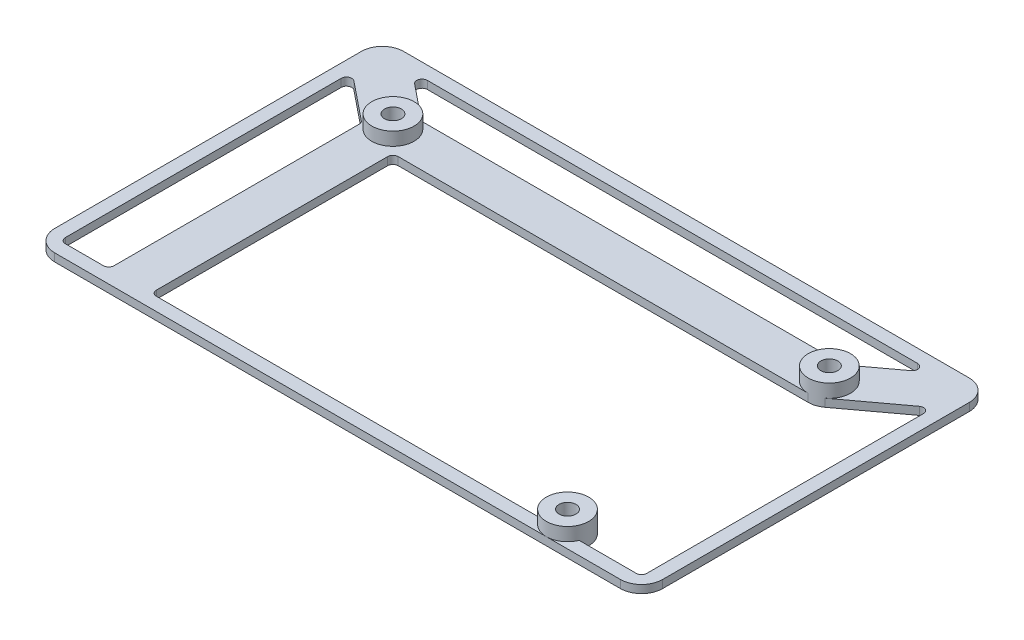
SolidWorks part; units mm, degrees
ref_plane "Alzado" through (0, 0, 0) normal (0, 0, 1) x (1, 0, 0)
ref_plane "Planta" through (0, 0, 0) normal (0, 1, 0) x (1, 0, 0)
ref_plane "Vista lateral" through (0, 0, 0) normal (1, 0, 0) x (0, 0, -1)
sketch "Croquis1" plane through (0, 0, 0) normal (0, 1, 0) x (1, 0, 0)
  line L1 (0, 4) -> (82.55, 4)
  line L2 (86.5486, -0.1052) -> (85.2786, -48.3652)
  line L3 (-2.0422, -3.4394) -> (79.2378, -51.6994)
  line L4 (0, -4) -> (82.55, -4)
  line L6 (1.098, 4) -> (83.3222, -44.8206)
  line L7 (78.5514, 0.1052) -> (77.2814, -48.1548)
  circle A1 centre (0, 0) radius 1.6
  circle A2 centre (82.55, 0) radius 1.6
  circle A3 centre (81.28, -48.26) radius 1.6
  circle A4 centre (0, 0) radius 4
  circle A5 centre (82.55, 0) radius 4
  circle A6 centre (81.28, -48.26) radius 4
  dimension "D1" = 3.2
  dimension "D7" = 8
  dimension "D3" = 82.55
  dimension "D6" = 1.27
extrude "Saliente-Extruir1" add sketch "Croquis1" along normal blind 1.5 contours A6 A3 | A6 L2 A5 L4 L7 L6 | A5 L1 L6 L4 L7 | A6 L7 L6 L4 A4 L3 | A6 L6 L7 | A5 L7 L4 | A5 A2 | A4 L4 L6 | A4 A1 region at (1.0289, 0, -3.7482) region at (43.2914, 0, -0.1461) region at (41.9356, 0, 25.0748) region at (7.0318, 0, 1.9303) region at (85.2984, 0, -2.7484) region at (77.8771, 0, 50.1382) region at (79.3885, 0, 3.0794) region at (78.8496, 0, 43.8567) region at (82.0449, 0, 23.7173)
extrude "Saliente-Extruir2" add sketch "Croquis1<3>" along normal blind 4 contours A4 A1 | A5 A2 | A6 A3 region at (1.0289, 0, -3.7482) region at (85.2984, 0, -2.7484) region at (77.8771, 0, 50.1382)
sketch "Croquis1<3>" plane through (0, 0, 0) normal (0, 1, 0) x (1, 0, 0) same geometry as "Croquis1"
sketch "Croquis2" plane through (0, 0, 0) normal (0, -1, 0) x (1, 0, 0)
  line L0 (14.5717, 4) -> (77.4607, 41.3403) construction
  line L1 (99.28, -13.74) -> (-15.72, -13.74)
  line L2 (99.28, -13.74) -> (99.28, 52.26)
  line L3 (99.28, 52.26) -> (-15.72, 52.26)
  line L4 (-15.72, -13.74) -> (-15.72, 52.26)
  line L5 (99.28, -13.74) -> (-15.72, 52.26) construction
  line L6 (99.28, 52.26) -> (-15.72, -13.74) construction
  line L7 (14.5717, 4) -> (78.4434, 4) construction
  line L8 (78.4434, 4) -> (77.4607, 41.3403) construction
  line L9 (14.5717, 4) -> (77.4607, 41.3403)
  line L10 (14.5717, 4) -> (78.4434, 4)
  line L11 (78.4434, 4) -> (77.4607, 41.3403)
  arc A1 (85.2786, 48.3652) -> (79.2378, 51.6994) centre (81.28, 48.26) ccw construction
  circle A2 centre (81.28, 48.26) radius 1.6 construction
  point P0 (41.78, 19.26)
  arc M5 (85.2786, 48.3652) -> (79.2378, 51.6994) centre (81.28, 48.26) ccw
  line M6 (79.2378, 51.6994) -> (-2.0422, 3.4394)
  arc M7 (-2.0422, 3.4394) -> (2.0422, -3.4394) centre (0, 0) ccw
  line M8 (2.0422, -3.4394) -> (1.098, -4)
  line M9 (1.098, -4) -> (82.55, -4)
  arc M10 (82.55, -4) -> (86.5486, 0.1052) centre (82.55, 0) ccw
  line M11 (86.5486, 0.1052) -> (85.2786, 48.3652)
  circle M12 centre (81.28, 48.26) radius 1.6
  circle M13 centre (82.55, 0) radius 1.6
  circle M14 centre (0, 0) radius 1.6
  line M15 (77.4607, 41.3403) -> (78.4434, 4)
  line M16 (78.4434, 4) -> (14.5717, 4)
  line M17 (14.5717, 4) -> (77.4607, 41.3403)
  dimension "D1" = 66
  dimension "D2" = 18
  dimension "D3" = 115
extrude "Saliente-Extruir7" add sketch "Croquis2" against normal up to surface (1.5 mm away) contours M11 M5 M6 M7 M8 M9 M10 M12 M14 M17 M15 M16 M13 | L4 L1 L2 L3 M5 M11 M10 M9 M8 M7 M6 region at (83.3272, 0, 50.3617) region at (41.78, 0, -12.4141) up to face at (56.8253, 1.5, 16.4468)
sketch "Croquis4" plane through (0, 1.5, 0) normal (0, 1, 0) x (1, 0, 0)
  line L4 (4, -4) -> (82.55, -4)
  line L5 (-4, 0) -> (-4, -49.76)
  line L6 (96.78, -49.76) -> (81.28, -49.76) construction
  line L8 (99.28, -52.26) -> (81.28, -52.26)
  line L9 (81.28, -52.26) -> (-15.72, -52.26)
  line L10 (-15.72, 13.74) -> (-15.72, -52.26)
  line L11 (99.28, 13.74) -> (-15.72, 13.74)
  line L12 (99.28, 13.74) -> (99.28, -52.26)
  line L13 (96.78, 11.24) -> (96.78, -49.76)
  line L14 (96.78, -49.76) -> (84.9881, -49.76)
  line L15 (77.5719, -49.76) -> (-13.22, -49.76)
  line L16 (-13.22, 11.24) -> (-13.22, -49.76)
  line L17 (96.78, 11.24) -> (-13.22, 11.24)
  line L18 (84.9304, -3.2146) -> (96.78, 5.56)
  line L19 (91.0074, 11.24) -> (81.2302, 4)
  line L20 (96.78, 5.56) -> (96.78, 11.24) construction
  line L21 (91.0074, 11.24) -> (96.78, 11.24) construction
  line L22 (1.4115, 4) -> (-7.57, 11.24)
  line L23 (-4, -1.9134) -> (-13.22, 5.5189)
  line L24 (81.2302, 4) -> (1.4115, 4)
  line L26 (14.5717, -4) -> (78.4434, -4) construction
  line L30 (4, -4) -> (4, -49.76)
  line L35 (81.28, -49.76) -> (-13.22, -49.76) construction
  circle A0 centre (82.55, 0) radius 4 construction
  circle A1 centre (82.55, 0) radius 4 construction
  circle A2 centre (0, 0) radius 4 construction
  circle A3 centre (0, 0) radius 4 construction
  circle A4 centre (0, 0) radius 4
  circle A5 centre (81.28, -48.26) radius 4
  circle A7 centre (81.28, -48.26) radius 4 construction
  circle A8 centre (82.55, 0) radius 4
  circle M13 centre (81.28, -48.26) radius 4
  circle M19 centre (82.55, 0) radius 4
  line M20 (78.4434, -4) -> (77.4607, -41.3403)
  line M21 (77.4607, -41.3403) -> (14.5717, -4)
  dimension "D1" = 2.5
  dimension "D2" = 5.68
  dimension "D3" = 5.65
extrude "Cortar-Extruir1" cut sketch "Croquis4" against normal blind 10 contours L4 L30 L15 L14 L13 L18 M13 M19 M20 M21 | L24 L19 L17 L22 | L5 L23 L16 L15 region at (48.3729, 1.5, 30.1531) region at (-8.7207, 1.5, 23.934) region at (41.5268, 1.5, -7.7469)
fillet "Redondeo1" radius 1 12 edges at (4, 0.75, 4) (4, 0.75, 49.76) (-4, 0.75, 49.76) (-13.22, 0.75, 49.76) (-4, 0.75, 1.9134) (-13.22, 0.75, -5.5189) (-7.57, 0.75, -11.24) (1.4115, 0.75, -4) (96.78, 0.75, 49.76) (81.2302, 0.75, -4) (91.0074, 0.75, -11.24) (96.78, 0.75, -5.56)
fillet "Redondeo2" radius 4 4 edges at (-15.72, 0.75, 52.26) (-15.72, 0.75, -13.74) (99.28, 0.75, -13.74) (99.28, 0.75, 52.26)
